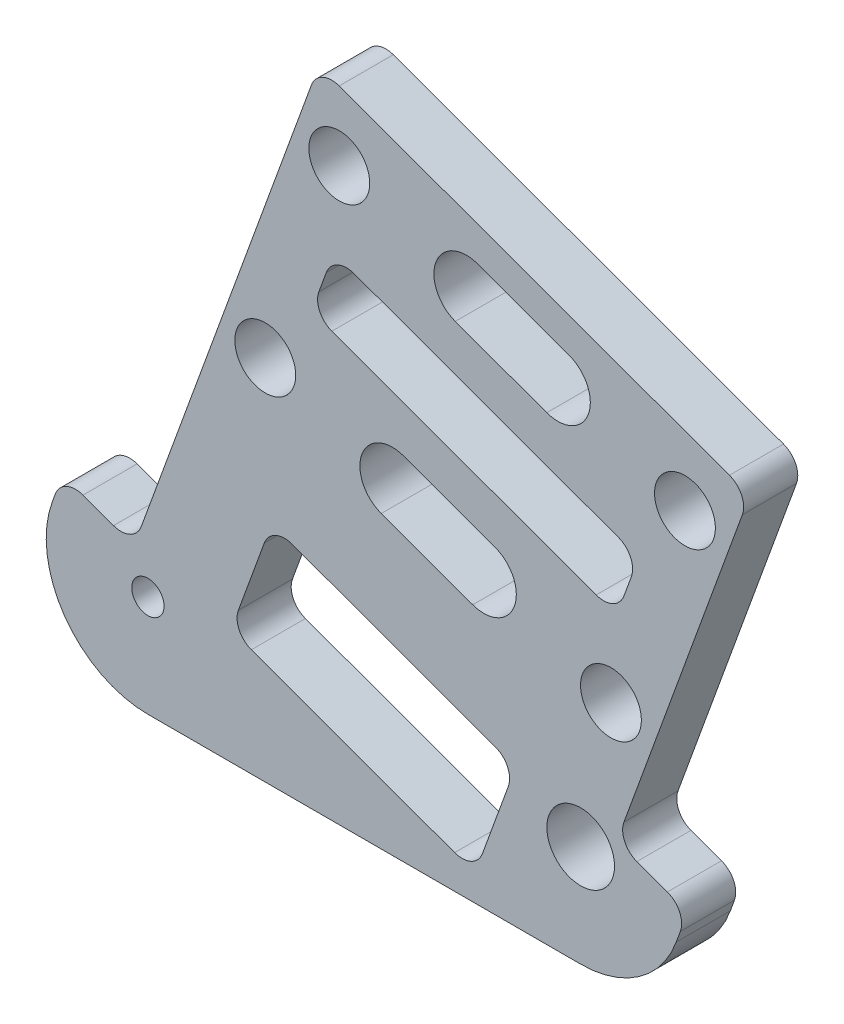
SolidWorks part; units mm, degrees
ref_plane "前视基准面" through (0, 0, 0) normal (0, 0, 1) x (1, 0, 0)
ref_plane "上视基准面" through (0, 0, 0) normal (0, 1, 0) x (1, 0, 0)
ref_plane "右视基准面" through (0, 0, 0) normal (1, 0, 0) x (0, 0, -1)
other "Configuration Table"
sketch "草图1" plane through (0, 0, 0) normal (0, 0, 1) x (1, 0, 0)
  line L5 (0, 0) -> (-11.9341, 0) construction
  line L6 (0, 0) -> (50.8, 0) construction
  line L7 (0, 0) -> (50.8, 0) construction
  line L8 (50.8, 0) -> (63.5, 0) construction
  line L9 (-11.2144, 4.0817) -> (-10.0042, 7.4066)
  line L19 (63.3632, -0.3759) -> (63.5, 0)
  line L20 (41.1014, 43.1393) -> (12.2558, -36.1133) construction
  line L21 (13.7757, 31.1876) -> (54.3517, 16.4191) construction
  line L22 (28.6934, 25.758) -> (39.4341, 21.8487) construction
  line L23 (29.9965, 29.3382) -> (40.7371, 25.4289)
  line L24 (27.3903, 22.1778) -> (38.131, 18.2685)
  line L25 (63.5, 0) -> (62.0144, -4.0817)
  line L32 (0, -11.9341) -> (50.8, -11.9341)
  line L43 (36.0776, 46.0459) -> (46.8183, 42.1367)
  line L44 (38.6838, 53.2064) -> (49.4245, 49.2971)
  line L45 (37.3807, 49.6262) -> (48.1214, 45.7169) construction
  line L47 (20.0679, 64.0365) -> (70.6465, 45.6274)
  line L52 (0, 0) -> (0, -11.9341)
  line L53 (14.5304, 14.6948) -> (9.7524, 1.5673)
  line L54 (9.7524, 1.5673) -> (38.3942, -8.8575)
  line L55 (38.3942, -8.8575) -> (43.1722, 4.27)
  line L56 (43.1722, 4.27) -> (14.5304, 14.6948)
  line L57 (-10.0042, 7.4066) -> (-1.6503, 4.3661)
  line L58 (-1.6503, 4.3661) -> (20.0679, 64.0365)
  line L59 (70.6465, 45.6274) -> (55.0093, 2.6647)
  line L60 (55.0093, 2.6647) -> (63.3632, -0.3759)
  line L61 (21.8093, 45.8331) -> (57.6116, 32.8022)
  line L62 (57.6116, 32.8022) -> (55.0054, 25.6417)
  line L63 (55.0054, 25.6417) -> (19.2031, 38.6727)
  line L64 (19.2031, 38.6727) -> (21.8093, 45.8331)
  circle A3 centre (50.8, 0) radius 3.9687
  circle A12 centre (54.3517, 16.4191) radius 3.5719
  circle A13 centre (13.7757, 31.1876) radius 3.5719
  arc A22 (29.9965, 29.3382) -> (27.3903, 22.1778) centre (28.6934, 25.758) ccw
  arc A23 (38.131, 18.2685) -> (40.7371, 25.4289) centre (39.4341, 21.8487) ccw
  arc A32 (-11.2144, 4.0817) -> (0, -11.9341) centre (0, 0) ccw
  arc A33 (50.8, -11.9341) -> (62.0144, -4.0817) centre (50.8, 0) ccw
  circle A34 centre (22.4631, 55.0557) radius 3.5719
  arc A35 (38.6838, 53.2064) -> (36.0776, 46.0459) centre (37.3807, 49.6262) ccw
  arc A36 (46.8183, 42.1367) -> (49.4245, 49.2971) centre (48.1214, 45.7169) ccw
  circle A37 centre (63.039, 40.2873) radius 3.5719
  point P2 (38.3178, 35.4913)
  point P11 (25.4, 0)
  point P18 (34.0637, 23.8033)
  point P24 (64.6392, 47.9687)
  point P26 (28.7705, 38.9662)
  point P38 (47.865, 32.0164)
  point P39 (38.3178, 35.4913)
  point P40 (42.751, 47.6715)
  point P46 (28.8513, 9.4824)
  point P49 (45.3572, 54.832)
  point P59 (39.7105, 39.3177)
  dimension "D9" = 7.9375
  dimension "D10" = 43.18
  dimension "D14" = 2
  dimension "D6" = 7.1437
  dimension "D13" = 3.81
  dimension "D8" = 11.9341
  dimension "D1" = 12.7
  dimension "D2" = 50.8
  dimension "D3" = 70
  dimension "D4" = 70
  dimension "D5" = 71.12
  dimension "D15" = 53.8246
  dimension "D16" = 10.16
  dimension "D17" = 10.16
  dimension "D18" = 25.4
  dimension "D19" = 30.48
  dimension "D21" = 13.97
  dimension "D11" = 33.02
  dimension "D12" = 11.43
  dimension "D22" = 15.24
  dimension "D23" = 63.5
  dimension "D24" = 8.89
  dimension "D25" = 45.72
  dimension "D26" = 8.89
  dimension "D27" = 38.1
  dimension "D28" = 7.62
  dimension "D29" = 16.51
extrude "Boss-Extrude1" add sketch "草图1" along normal blind 6.35 contours L32 A33 L25 L19 L60 L59 L47 L58 L57 L9 A32 A37 A36 L43 A35 L44 A23 L24 A22 L23 L63 L64 L61 L62 L56 L55 L54 L53 A3 A12 A13 A34 region at (30.3826, 19.5043, 0)
fillet "Fillet1" radius 2.54 14 edges at (43.1722, 4.27, 3.175) (38.3942, -8.8575, 3.175) (9.7524, 1.5673, 3.175) (14.5304, 14.6948, 3.175) (-1.6503, 4.3661, 3.175) (55.0093, 2.6647, 3.175) (55.0054, 25.6417, 3.175) (57.6116, 32.8022, 3.175) (19.2031, 38.6727, 3.175) (21.8093, 45.8331, 3.175) (70.6465, 45.6274, 3.175) (20.0679, 64.0365, 3.175) (-10.0042, 7.4066, 3.175) (63.3632, -0.3759, 3.175)
sketch "Sketch1" plane through (0, 0, 6.35) normal (0, 0, 1) x (1, 0, 0)
  point P0 (0, 0)
hole_wizard "#10-24 Tapped Hole1" positions "Sketch1" profile "Sketch2" tap size "#10-24" standard "ANSI Inch" end condition through all
sketch "Sketch2" plane through (0, 0, 6.35) normal (1, 0, 0) x (0, -1, 0)
  line L0 (0, 0) -> (0, 6.35)
  line L1 (0, 6.35) -> (1.8986, 6.35)
  line L2 (1.8986, 6.35) -> (1.8986, 0)
  line L5 (1.8986, 0) -> (0, 0)
  line L11 (0, -6.35) -> (0, 107.95) construction
  dimension "Thru Tap Drill Dia." = 3.7973
  dimension "Thru Tap Drill Depth" = 6.35
cosmetic thread "Hole Thread1" parameters "D2"=4.826
